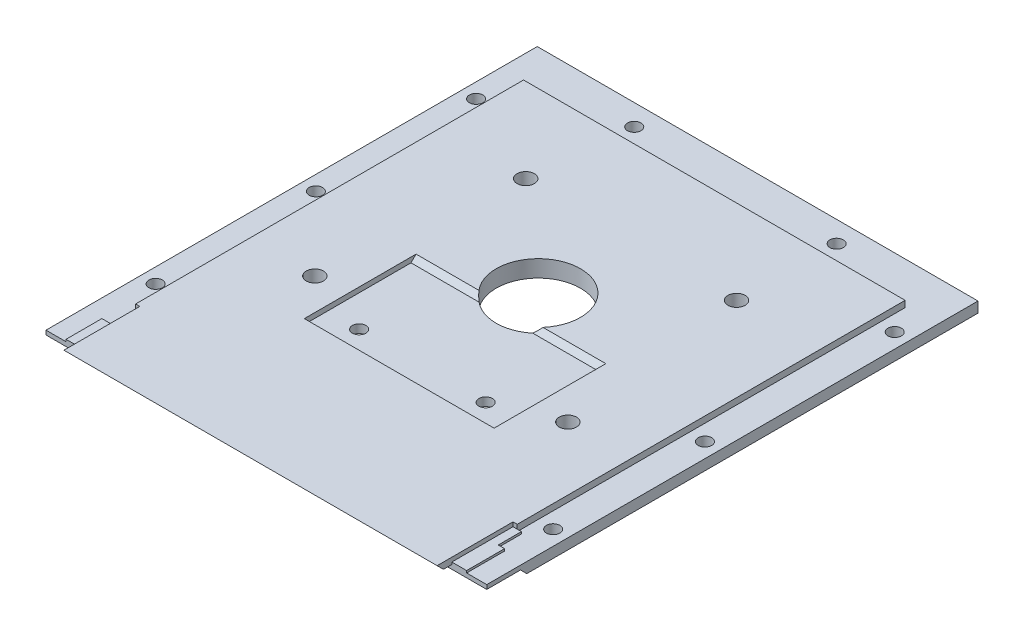
SolidWorks part; units mm, degrees
ref_plane "前视基准面" through (0, 0, 0) normal (0, 0, 1) x (1, 0, 0)
ref_plane "上视基准面" through (0, 0, 0) normal (0, 1, 0) x (1, 0, 0)
ref_plane "右视基准面" through (0, 0, 0) normal (1, 0, 0) x (0, 0, -1)
other "Configuration Table"
sketch "草图1" plane through (0, 0, 0) normal (0, 1, 0) x (1, 0, 0)
  line L1 (0, 0) -> (90.5, 0)
  line L2 (0, 0) -> (0, 97)
  line L3 (0, 97) -> (90.5, 97)
  line L4 (90.5, 0) -> (90.5, 97)
  dimension "D1" = 90.5
  dimension "D2" = 97
extrude "凸台-拉伸1" add sketch "草图1" along normal blind 2
sketch "草图2" plane through (0, 0, 0) normal (0, -1, 0) x (1, 0, 0)
  line L0 (45.25, 0) -> (45.25, -97) construction
  line L1 (0, 0) -> (90.5, 0) construction
  line L2 (90.5, -97) -> (0, -97) construction
  line L3 (-3.25, -13) -> (-3.25, -89) construction
  line L4 (-6.75, 17) -> (97.775, 17)
  line L5 (-6.75, 17) -> (-6.75, -107)
  line L6 (-6.75, -107) -> (97.775, -107)
  line L7 (97.775, 17) -> (97.775, -107)
  line L8 (94.275, -90.75) -> (94.275, -9.75) construction
  circle A0 centre (21.25, -102) radius 1.6
  circle A1 centre (69.25, -102) radius 1.6
  circle A2 centre (-3.25, -89) radius 1.6
  circle A3 centre (94.275, -90.75) radius 1.6
  circle A4 centre (-3.25, -13) radius 1.6
  circle A5 centre (-3.25, -51) radius 1.6
  circle A6 centre (94.275, -9.75) radius 1.6
  circle A7 centre (94.275, -45.75) radius 1.6
  dimension "D1" = 3.2
  dimension "D2" = 48
  dimension "D3" = 5
  dimension "D4" = 5
  dimension "D5" = 24.5
  dimension "D6" = 3.5
  dimension "D7" = 13
  dimension "D8" = 25.025
  dimension "D9" = 11.25
  dimension "D11" = 38
  dimension "D12" = 45
  dimension "D13" = 36
  dimension "D10" = 3.5
  dimension "D14" = 114
extrude "凸台-拉伸2" add sketch "草图2" along normal blind 2.5
sketch "草图3" plane through (0, 0, 0) normal (0, 1, 0) x (1, 0, 0)
  line L0 (0, 0) -> (90.5, 0) construction
  line L1 (1, 0) -> (89.5, 0)
  line L2 (1, 0) -> (1, -17)
  line L3 (1, -17) -> (89.5, -17)
  line L4 (89.5, 0) -> (89.5, -17)
  line L5 (97.775, -17) -> (-6.75, -17) construction
  line L6 (0, 97) -> (0, 0) construction
  line L7 (90.5, 0) -> (90.5, 97) construction
  dimension "D1" = 1
  dimension "D2" = 1
extrude "凸台-拉伸3" add sketch "草图3" along normal up to surface (2 mm away) up to face at (45.25, 2, -48.5)
sketch "草图4" plane through (0, 0, 0) normal (0, 1, 0) x (1, 0, 0)
  line L0 (0, 97) -> (0, 0) construction
  line L1 (1, 0) -> (0, 0)
  line L2 (1, 0) -> (1, 5)
  line L3 (1, 5) -> (0, 5)
  line L4 (0, 0) -> (0, 5)
  line L5 (90.5, 0) -> (90.5, 97) construction
  line L6 (89.5, 0) -> (90.5, 0)
  line L7 (89.5, 0) -> (89.5, 5)
  line L8 (89.5, 5) -> (90.5, 5)
  line L9 (90.5, 0) -> (90.5, 5)
  dimension "D1" = 5
extrude "切除-拉伸1" cut sketch "草图4" along normal up to surface (2 mm away) up to face at (45.25, 2, -20)
sketch "草图5" plane through (97.775, 0, 0) normal (1, 0, 0) x (0, 0, -1)
  line L0 (-8.5, -2.5) -> (-8.5, 0)
  line L1 (107, -2.5) -> (-17, -2.5) construction
  line L2 (107, 0) -> (-17, 0) construction
  line L4 (5, 2) -> (-17, 2) construction
  line L5 (-11.5, 2) -> (-17, 2)
  line L6 (-17, 2) -> (-17, -2.5)
  line L7 (-17, -2.5) -> (-8.5, -2.5)
  line L8 (-11.5, 2) -> (-9.5, 0)
  line L9 (-17, 0) -> (5, 0) construction
  line L10 (-9.5, 0) -> (-8.5, 0)
  dimension "D1" = 8.5
  dimension "D2" = 1
  dimension "D3" = 45
extrude "切除-拉伸2" cut sketch "草图5" against normal through all
sketch "草图6" plane through (0, 2, 0) normal (0, 1, 0) x (1, 0, 0)
  line L0 (45.5125, 107) -> (45.5125, 47) construction
  line L1 (68.0125, 22) -> (23.0125, 22)
  line L2 (68.0125, 22) -> (68.0125, 47)
  line L3 (68.0125, 47) -> (23.0125, 47)
  line L4 (23.0125, 22) -> (23.0125, 47)
  line L5 (-6.75, 107) -> (97.775, 107) construction
  line L7 (90.5, 97) -> (0, 97) construction
  dimension "D1" = 25
  dimension "D2" = 45
  dimension "D3" = 50
extrude "切除-拉伸3" cut sketch "草图6" against normal blind 1.7
sketch "草图7" plane through (0, 0.3, 0) normal (0, 1, 0) x (1, 0, 0)
  line L0 (23.0125, 27.5) -> (68.0125, 27.5) construction
  line L1 (23.0125, 47) -> (23.0125, 22) construction
  line L2 (68.0125, 22) -> (68.0125, 47) construction
  line L3 (23.0125, 22) -> (68.0125, 22) construction
  line L4 (45.5125, 47) -> (45.5125, 22) construction
  line L5 (68.0125, 47) -> (23.0125, 47) construction
  line L6 (23.0125, 22) -> (68.0125, 22) construction
  circle A0 centre (30.5125, 27.5) radius 1.6
  circle A1 centre (60.5125, 27.5) radius 1.6
  dimension "D2" = 30
  dimension "D3" = 3.2
  dimension "D1" = 5.5
extrude "切除-拉伸4" cut sketch "草图7" against normal up to next
chamfer "倒角1" distance 2 angle 45 1 edges at (45.5125, 2, -47)
sketch "草图8" plane through (0, 2, 0) normal (0, 1, 0) x (1, 0, 0)
  line L0 (45.5125, 107) -> (45.5125, -11.5) construction
  line L1 (-6.75, 107) -> (97.775, 107) construction
  line L3 (20.5125, 77) -> (70.5125, 77) construction
  line L4 (1, -11.5) -> (89.5, -11.5) construction
  line L5 (90.5, 97) -> (0, 97) construction
  circle A0 centre (20.5125, 77) radius 2.05
  circle A1 centre (70.5125, 77) radius 2.05
  circle A2 centre (15.5125, 32) radius 2.05
  circle A3 centre (75.5125, 32) radius 2.05
  dimension "D1" = 4.1
  dimension "D4" = 60
  dimension "D2" = 50
  dimension "D3" = 20
  dimension "D5" = 45
extrude "切除-拉伸5" cut sketch "草图8" against normal up to next
sketch "草图9" plane through (0, 2, 0) normal (0, 1, 0) x (1, 0, 0)
  line L0 (45.5125, 107) -> (45.5125, 55) construction
  line L1 (-6.75, 107) -> (97.775, 107) construction
  circle A0 centre (45.5125, 55) radius 10
  dimension "D1" = 20
  dimension "D2" = 52
extrude "切除-拉伸6" cut sketch "草图9" against normal up to next
sketch "草图10" plane through (0, -2.5, 0) normal (0, -1, 0) x (1, 0, 0)
  line L1 (27.7625, -25.9123) -> (27.7625, -29.0877)
  line L2 (27.7625, -29.0877) -> (30.5125, -30.6754)
  line L3 (30.5125, -30.6754) -> (33.2625, -29.0877)
  line L4 (33.2625, -29.0877) -> (33.2625, -25.9123)
  line L5 (33.2625, -25.9123) -> (30.5125, -24.3246)
  line L6 (30.5125, -24.3246) -> (27.7625, -25.9123)
  line L7 (57.7625, -25.9123) -> (57.7625, -29.0877)
  line L8 (57.7625, -29.0877) -> (60.5125, -30.6754)
  line L9 (60.5125, -30.6754) -> (63.2625, -29.0877)
  line L10 (63.2625, -29.0877) -> (63.2625, -25.9123)
  line L11 (63.2625, -25.9123) -> (60.5125, -24.3246)
  line L12 (60.5125, -24.3246) -> (57.7625, -25.9123)
  circle A0 centre (30.5125, -27.5) radius 2.75 construction
  circle A1 centre (60.5125, -27.5) radius 2.75 construction
  dimension "D1" = 5.5
extrude "切除-拉伸7" cut sketch "草图10" against normal blind 0.8
sketch "草图11" plane through (97.775, 0, 0) normal (1, 0, 0) x (0, 0, -1)
  line L0 (107, -2.5) -> (-8.5, -2.5) construction
  line L1 (-8.5, 0) -> (-2, 0)
  line L2 (-8.5, 0) -> (-8.5, -2.5)
  line L3 (-8.5, -2.5) -> (-2, -2.5)
  line L4 (-2, 0) -> (-2, -2.5)
  dimension "D1" = 6.5
extrude "切除-拉伸8" cut sketch "草图11" against normal up to next
chamfer "倒角2" distance 2 angle 45 1 edges at (45.5125, -2.5, 2)
sketch "草图12" plane through (0, 0, 0) normal (0, -1, 0) x (1, 0, 0)
  line L0 (1, 9.5) -> (89.5, 9.5) construction
  line L1 (-6.75, 0) -> (97.775, 0)
  line L2 (-6.75, 0) -> (-6.75, 9.5)
  line L3 (-6.75, 9.5) -> (97.775, 9.5)
  line L4 (97.775, 0) -> (97.775, 9.5)
  line L6 (97.775, 0) -> (-6.75, 0) construction
extrude "凸台-拉伸4" add sketch "草图12" along normal blind 1
sketch "草图13" plane through (0, 0, 0) normal (0, 1, 0) x (1, 0, 0)
  line L0 (1, -11.5) -> (1, 5) construction
  line L1 (1, 5) -> (-1, 5)
  line L2 (1, 5) -> (1, -9.5)
  line L3 (1, -9.5) -> (-1, -9.5)
  line L4 (-1, 5) -> (-1, -9.5)
  line L5 (89.5, 5) -> (91.5, 5)
  line L6 (89.5, 5) -> (89.5, -9.5)
  line L7 (89.5, -9.5) -> (91.5, -9.5)
  line L8 (91.5, 5) -> (91.5, -9.5)
  line L9 (1, -9.5) -> (-6.75, -9.5) construction
  dimension "D1" = 2
  dimension "D2" = 2
extrude "凸台-拉伸5" add sketch "草图13" along normal blind 0.5
sketch "草图14" plane through (0, 0, 0) normal (0, 1, 0) x (1, 0, 0)
  line L0 (97.775, -9.5) -> (91.5, -9.5) construction
  line L1 (93, -9.5) -> (91.5, -9.5)
  line L2 (93, -9.5) -> (93, -0.5)
  line L3 (93, -0.5) -> (91.5, -0.5)
  line L4 (91.5, -9.5) -> (91.5, -0.5)
  line L6 (-1, -9.5) -> (-6.75, -9.5) construction
  line L7 (-2, -9.5) -> (-1, -9.5)
  line L8 (-2, -9.5) -> (-2, -0.5)
  line L9 (-2, -0.5) -> (-1, -0.5)
  line L10 (-1, -9.5) -> (-1, -0.5)
  line L11 (-1, 5) -> (-1, -9.5) construction
  line L12 (91.5, -9.5) -> (91.5, 5) construction
  dimension "D1" = 1
  dimension "D2" = 1.5
  dimension "D3" = 9
extrude "凸台-拉伸6" add sketch "草图14" along normal up to surface (0.5 mm away) up to face at (0, 0.5, 0.8)
sketch "草图15" plane through (0, -4.75, 4.75) normal (0, -0.7071, 0.7071) x (1, 0, 0)
  line L4 (89.5, 9.5459) -> (1, 9.5459)
  line L5 (1, 9.5459) -> (1, 6.7175)
  line L6 (1, 6.7175) -> (89.5, 6.7175)
  line L7 (89.5, 6.7175) -> (89.5, 9.5459)
  line L8 (89.5, 9.5459) -> (1, 9.5459)
  line L9 (1, 9.5459) -> (1, 6.7175)
  line L10 (1, 6.7175) -> (89.5, 6.7175)
  line L11 (89.5, 6.7175) -> (89.5, 9.5459)
  dimension "D1" = 0
extrude "凸台-拉伸7" add sketch "草图15" along direction (0, 0, 1) on the side of the normal blind 2
sketch "草图16" plane through (0, 2, 0) normal (0, 1, 0) x (1, 0, 0)
  line L8 (1, 5) -> (1, -13.5)
  line L9 (1, -13.5) -> (89.5, -13.5)
  line L10 (89.5, -13.5) -> (89.5, 5)
  line L11 (89.5, 5) -> (90.5, 5)
  line L12 (90.5, 5) -> (90.5, 97)
  line L13 (90.5, 97) -> (0, 97)
  line L14 (0, 97) -> (0, 5)
  line L15 (0, 5) -> (1, 5)
  line L16 (1, 5) -> (1, -13.5)
  line L17 (1, -13.5) -> (89.5, -13.5)
  line L18 (89.5, -13.5) -> (89.5, 5)
  line L19 (89.5, 5) -> (90.5, 5)
  line L20 (90.5, 5) -> (90.5, 97)
  line L21 (90.5, 97) -> (0, 97)
  line L22 (0, 97) -> (0, 5)
  line L23 (0, 5) -> (1, 5)
  dimension "D1" = 0
extrude "切除-拉伸9" cut sketch "草图16" against normal blind 0.5
sketch "草图17" plane through (0, 0.5, 0) normal (0, 1, 0) x (1, 0, 0)
  line L0 (-2, -9.5) -> (-2, -0.5) construction
  line L1 (0, 5) -> (-2, 5)
  line L2 (0, 5) -> (0, -1)
  line L3 (0, -1) -> (-2, -1)
  line L4 (-2, 5) -> (-2, -1)
  dimension "D1" = 6
extrude "切除-拉伸10" cut sketch "草图17" against normal up to surface (0.5 mm away) up to face at (94.275, 0, -47.35)
